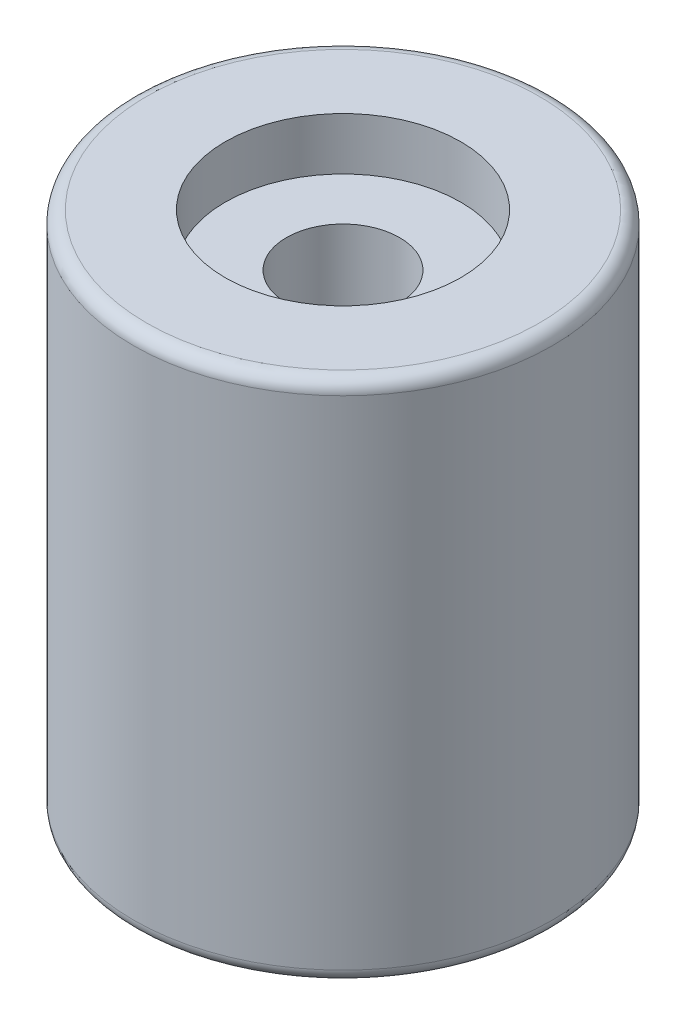
SolidWorks part; units mm, degrees
ref_plane "Front Plane" through (0, 0, 0) normal (0, 0, 1) x (1, 0, 0)
ref_plane "Top Plane" through (0, 0, 0) normal (0, 1, 0) x (1, 0, 0)
ref_plane "Right Plane" through (0, 0, 0) normal (1, 0, 0) x (0, 0, -1)
sketch "Sketch1" plane through (0, 0, 0) normal (0, 1, 0) x (1, 0, 0)
  circle A4 centre (0, 0) radius 25.4
  dimension "D1" = 50.8
extrude "Boss-Extrude1" add sketch "Sketch1" along normal blind 63.5 contours A4
fillet "Fillet1" radius 1.5875 2 edges at (0, 0, 25.4) (0, 63.5, 25.4)
sketch "Sketch2" plane through (0, 63.5, 0) normal (0, 1, 0) x (1, 0, 0)
  circle A0 centre (0, 0) radius 14.2875
  dimension "D1" = 28.575
extrude "Cut-Extrude1" cut sketch "Sketch2" against normal blind 6.35
sketch "Sketch3" plane through (0, 0, 0) normal (0, -1, 0) x (1, 0, 0)
  circle A0 centre (0, 0) radius 14.2875
  dimension "D1" = 28.575
extrude "Cut-Extrude2" cut sketch "Sketch3" against normal blind 6.35
sketch "Sketch4" plane through (0, 6.35, 0) normal (0, -1, 0) x (1, 0, 0)
  circle A0 centre (0, 0) radius 6.858
  dimension "D1" = 13.716
extrude "Cut-Extrude3" cut sketch "Sketch4" against normal through all and the other way through all
